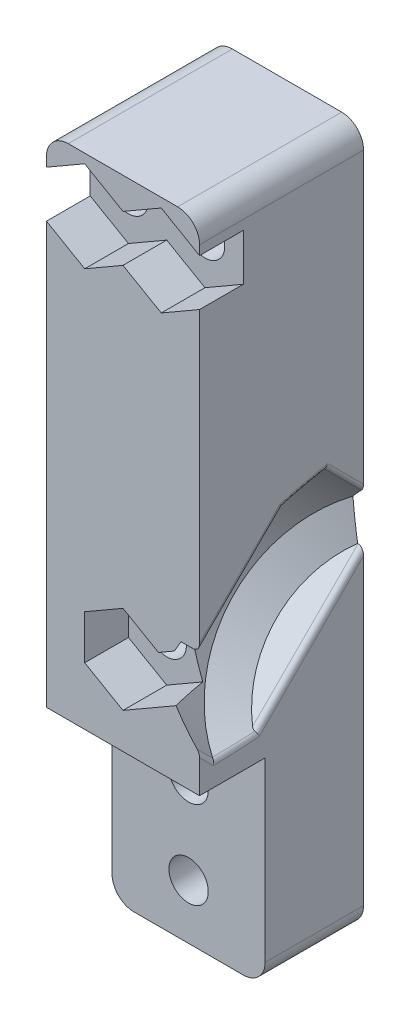
SolidWorks part; units mm, degrees
ref_plane "Front Plane" through (0, 0, 0) normal (0, 0, 1) x (1, 0, 0)
ref_plane "Top Plane" through (0, 0, 0) normal (0, 1, 0) x (1, 0, 0)
ref_plane "Right Plane" through (0, 0, 0) normal (1, 0, 0) x (0, 0, -1)
sketch "Sketch1" plane through (0, 0, 0) normal (0, 0, 1) x (1, 0, 0)
  line L1 (0, 0) -> (17.78, 0)
  line L2 (0, 0) -> (0, -81.0768)
  line L3 (0, -81.0768) -> (17.78, -81.0768)
  line L4 (17.78, 0) -> (17.78, -81.0768)
  line L5 (8.89, 0) -> (8.89, -81.0768) construction
  circle A0 centre (4.445, -6.35) radius 2.286
  circle A1 centre (8.89, -48.6918) radius 2.286
  circle A2 centre (8.89, -64.5668) radius 2.286
  circle A3 centre (8.89, -74.7268) radius 2.286
  circle A4 centre (13.335, -6.35) radius 2.286
  point P5 (8.89, 0)
  dimension "D3" = 4.572
  dimension "D1" = 17.78
  dimension "D2" = 81.0768
  dimension "D4" = 6.35
  dimension "D5" = 15.875
  dimension "D6" = 6.35
  dimension "D7" = 10.16
  dimension "D8" = 4.445
extrude "Boss-Extrude1" add sketch "Sketch1" along normal blind 19.05
sketch "Sketch2" plane through (0, 0, 19.05) normal (0, 0, 1) x (1, 0, 0)
  line L1 (4.445, -11.6293) -> (9.017, -8.9896)
  line L2 (9.017, -8.9896) -> (9.017, -3.7104)
  line L3 (9.017, -3.7104) -> (4.445, -1.0707)
  line L4 (4.445, -1.0707) -> (-0.127, -3.7104)
  line L5 (-0.127, -3.7104) -> (-0.127, -8.9896)
  line L6 (-0.127, -8.9896) -> (4.445, -11.6293)
  line L7 (8.89, -53.8244) -> (13.335, -51.2581)
  line L8 (13.335, -51.2581) -> (13.335, -46.1255)
  line L9 (13.335, -46.1255) -> (8.89, -43.5592)
  line L10 (8.89, -43.5592) -> (4.445, -46.1255)
  line L11 (4.445, -46.1255) -> (4.445, -51.2581)
  line L12 (4.445, -51.2581) -> (8.89, -53.8244)
  line L13 (13.335, -1.0707) -> (8.763, -3.7104)
  line L14 (8.763, -3.7104) -> (8.763, -8.9896)
  line L15 (8.763, -8.9896) -> (13.335, -11.6293)
  line L16 (13.335, -11.6293) -> (17.907, -8.9896)
  line L17 (17.907, -8.9896) -> (17.907, -3.7104)
  line L18 (17.907, -3.7104) -> (13.335, -1.0707)
  circle A0 centre (4.445, -6.35) radius 4.572 construction
  circle A1 centre (8.89, -48.6918) radius 4.445 construction
  circle A2 centre (13.335, -6.35) radius 4.572 construction
  circle M2 centre (4.445, -6.35) radius 2.286
  line M3 (0, 0) -> (0, -81.0768)
  line M5 (17.78, -81.0768) -> (17.78, 0)
  circle M24 centre (13.335, -6.35) radius 2.286
  dimension "D1" = 9.144
  dimension "D2" = 8.89
extrude "Cut-Extrude1" cut sketch "Sketch2" against normal blind 5.08 contours L15 L14 L13 L3 L4 L6 L1 M3 M2 | L18 L13 L3 L2 L1 L15 L16 M5 M24 | L14 L15 L1 L2 L3 L13 | L7 L8 L9 L10 L11 L12
sketch "Sketch3" plane through (0, 0, 19.05) normal (0, 0, 1) x (1, 0, 0)
  circle A0 centre (8.89, -64.5668) radius 4.445
  circle A1 centre (8.89, -74.7268) radius 4.445
  dimension "D1" = 8.89
extrude "Cut-Extrude2" [suppressed] cut sketch "Sketch3" against normal blind 2.54
fillet "Fillet1" radius 2.54 4 edges at (0, -81.0768, 9.525) (17.78, -81.0768, 9.525) (17.78, 0, 9.525) (0, 0, 9.525)
ref_plane "Plane1" through (0, -40.5384, -40.5384) normal (0, 0.7071, 0.7071) x (1, 0, 0)
ref_plane "Plane2" through (0, -21.2308, -21.2308) normal (0, 0.7071, 0.7071) x (1, 0, 0)
sketch "Sketch4" plane through (0, -21.2308, -21.2308) normal (0, 0.7071, 0.7071) x (1, 0, 0)
  circle A0 centre (26.67, -38.6619) radius 15.5575
  dimension "D1" = 31.115
  dimension "D2" = 26.67
  dimension "D3" = 38.6619
extrude "Cut-Extrude3" cut sketch "Sketch4" along normal blind 12.7
chamfer "Chamfer1" distance 3.175 angle 40 2 edges at (11.7938, -36.3689, 11.8677) (13.069, -53.9098, 11.4481)
fillet "Fillet2" radius 0.635 6 edges at (17.78, -38.5225, 14.0213) (17.78, -48.817, 6.3553) (17.78, -34.5326, 2.0879) (17.78, -54.5168, 18.2151)
sketch "Sketch5" plane through (25.5292, -44.2178, 0) normal (-0.5, 0.866, 0) x (0.866, 0.5, 0)
  line L0 (-19.2133, -19.05) -> (-14.0806, -19.05) construction
  line L1 (-19.2133, -13.97) -> (-5.7998, -13.97)
  line L2 (-19.2133, -13.97) -> (-19.2133, -19.05)
  line L3 (-19.2133, -19.05) -> (-5.7998, -19.05)
  line L4 (-5.7998, -13.97) -> (-5.7998, -19.05)
extrude "Cut-Extrude4" cut sketch "Sketch5" along normal up to vertex (4.7694 mm away)
sketch "Sketch6" plane through (0, 0, 19.05) normal (0, 0, 1) x (1, 0, 0)
  line L0 (0, -9.063) -> (0, -78.5368) construction
  line L1 (0, -57.9628) -> (17.78, -57.9628)
  line L2 (0, -57.9628) -> (0, -81.0768)
  line L3 (0, -81.0768) -> (17.78, -81.0768)
  line L4 (17.78, -57.9628) -> (17.78, -81.0768)
  line L5 (2.54, -81.0768) -> (15.24, -81.0768) construction
  line L6 (17.78, -78.5368) -> (17.78, -54.1449) construction
  dimension "D1" = 23.114
extrude "Cut-Extrude5" cut sketch "Sketch6" against normal blind 7.62
